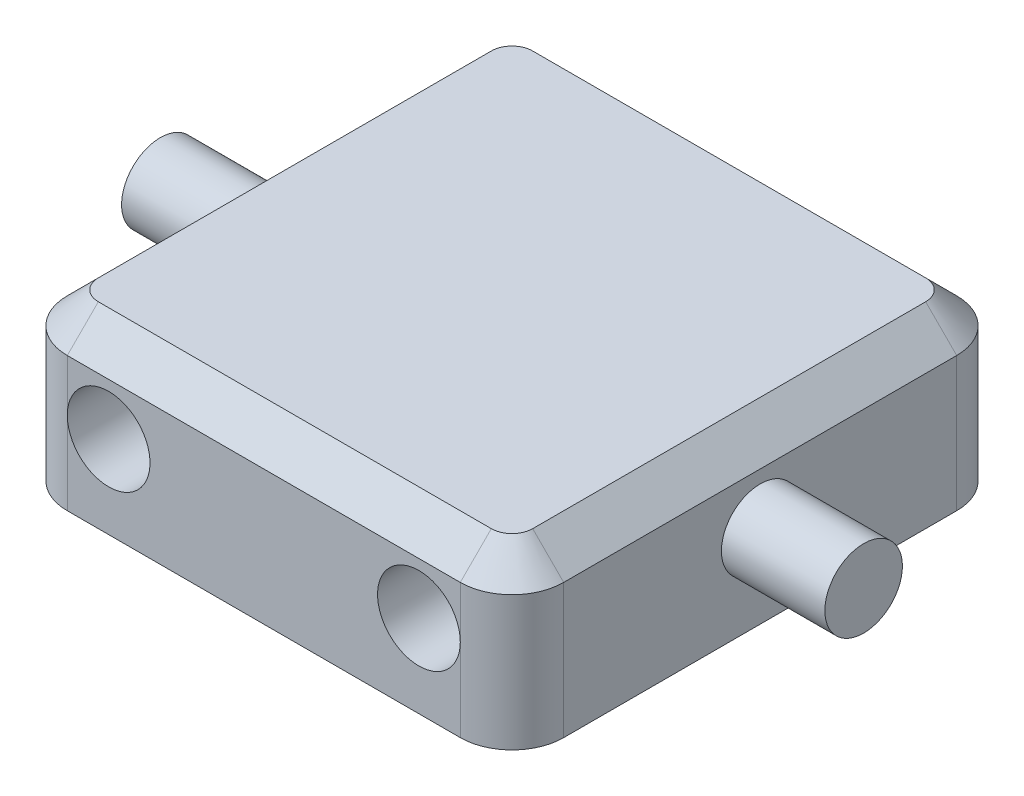
SolidWorks part; units mm, degrees
ref_plane "Front Plane" through (0, 0, 0) normal (0, 0, 1) x (1, 0, 0)
ref_plane "Top Plane" through (0, 0, 0) normal (0, 1, 0) x (1, 0, 0)
ref_plane "Right Plane" through (0, 0, 0) normal (1, 0, 0) x (0, 0, -1)
sketch "Sketch1" plane through (0, 0, 0) normal (0, 1, 0) x (1, 0, 0)
  line L1 (-24, -24) -> (24, -24)
  line L2 (-24, -24) -> (-24, 24)
  line L3 (-24, 24) -> (24, 24)
  line L4 (24, -24) -> (24, 24)
  line L5 (-24, -24) -> (24, 24) construction
  line L6 (-24, 24) -> (24, -24) construction
  point P0 (0, 0)
  dimension "D1" = 48
  dimension "D2" = 48
extrude "Boss-Extrude1" add sketch "Sketch1" along normal blind 16
sketch "Sketch2" plane through (0, 0, 24) normal (0, 0, 1) x (1, 0, 0)
  circle A0 centre (-15, 8) radius 4
  circle A1 centre (15, 8) radius 4
  dimension "D1" = 15
  dimension "D2" = 15
extrude "Cut-Extrude1" cut sketch "Sketch2" against normal blind 100
sketch "Sketch3" plane through (24, 0, 0) normal (1, 0, 0) x (0, 0, -1)
  line L0 (-24, 0) -> (24, 0) construction
  circle A0 centre (0, 8) radius 3.75
  dimension "D1" = 8
  dimension "D2" = 7.5
extrude "Boss-Extrude2" add sketch "Sketch3" along normal blind 10
mirror "Mirror1" about plane through (0, 0, 0) normal (1, 0, 0) of "Boss-Extrude2"
fillet "Fillet1" radius 5 4 edges at (24, 8, -24) (24, 8, 24) (-24, 8, -24) (-24, 8, 24)
chamfer "Chamfer1" distance 3 angle 45 8 edges at (22.5355, 16, 22.5355) (0, 16, 24) (-22.5355, 16, 22.5355) (-24, 16, 0) (-22.5355, 16, -22.5355) (0, 16, -24) (22.5355, 16, -22.5355) (24, 16, 0)
